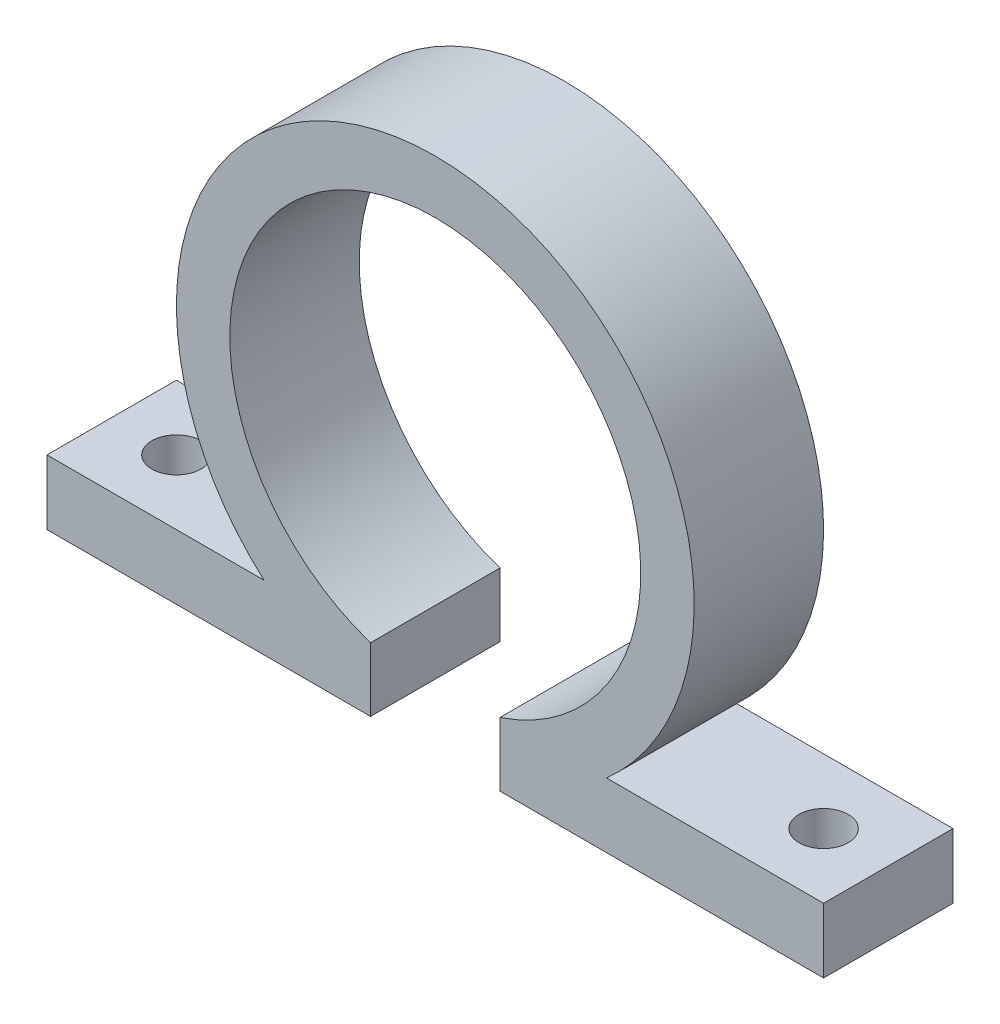
SolidWorks part; units mm, degrees
ref_plane "Front Plane" through (0, 0, 0) normal (0, 0, 1) x (1, 0, 0)
ref_plane "Top Plane" through (0, 0, 0) normal (0, 1, 0) x (1, 0, 0)
ref_plane "Right Plane" through (0, 0, 0) normal (1, 0, 0) x (0, 0, -1)
sketch "Sketch1" plane through (0, 0, 0) normal (0, 0, 1) x (1, 0, 0)
  circle A0 centre (0, 0) radius 20
  dimension "D1" = 40
extrude "Boss-Extrude1" add sketch "Sketch1" along normal blind 10
sketch "Sketch2" plane through (0, 0, 0) normal (0, 0, -1) x (-1, 0, 0)
  line L1 (30, -15) -> (-30, -15)
  line L2 (30, -15) -> (30, -20)
  line L3 (30, -20) -> (-30, -20)
  line L4 (-30, -15) -> (-30, -20)
  circle A0 centre (0, 0) radius 20 construction
  dimension "D2" = 20
  dimension "D1" = 5
  dimension "D3" = 60
  dimension "D4" = 30
extrude "Boss-Extrude2" add sketch "Sketch2" against normal blind 10
sketch "Sketch3" plane through (0, 0, 0) normal (0, 0, -1) x (-1, 0, 0)
  circle A0 centre (0, 0) radius 15.875
  dimension "D1" = 31.75
extrude "Cut-Extrude1" cut sketch "Sketch3" against normal through all
sketch "Sketch4" plane through (0, 0, 10) normal (0, 0, 1) x (1, 0, 0)
  line L0 (30, -20) -> (-30, -20) construction
  line L1 (-5, -15.067) -> (5, -15.067)
  line L2 (-5, -15.067) -> (-5, -20)
  line L3 (-5, -20) -> (5, -20)
  line L4 (5, -15.067) -> (5, -20)
  line L5 (-30, -20) -> (-30, -15) construction
  circle A0 centre (0, 0) radius 15.875 construction
  dimension "D1" = 25
  dimension "D2" = 10
extrude "Cut-Extrude2" cut sketch "Sketch4" against normal through all
hole_wizard "#6 Clearance Hole1" positions "Sketch6" profile "Sketch7" hole size "#6" standard "ANSI Inch" end condition through all
sketch "Sketch6" plane through (0, -15, 0) normal (0, 1, 0) x (1, 0, 0)
  line L0 (-30, 0) -> (-13.2288, 0) construction
  line L1 (-30, -10) -> (-30, 0) construction
  point P0 (-25, -5)
  dimension "D1" = 5
  dimension "D2" = 5
sketch "Sketch7" plane through (-25, -15, 5) normal (1, 0, 0) x (0, 0, 1)
  line L0 (0, 0) -> (0, 5)
  line L1 (0, 5) -> (1.8986, 5)
  line L2 (1.8986, 5) -> (1.8986, 0)
  line L5 (1.8986, 0) -> (0, 0)
  line L11 (0, -6.35) -> (0, 107.95) construction
  dimension "Thru Hole Dia." = 3.7973
  dimension "Thru Hole Depth" = 5
mirror "Mirror1" about plane through (0, 0, 0) normal (1, 0, 0) of "#6 Clearance Hole1"
